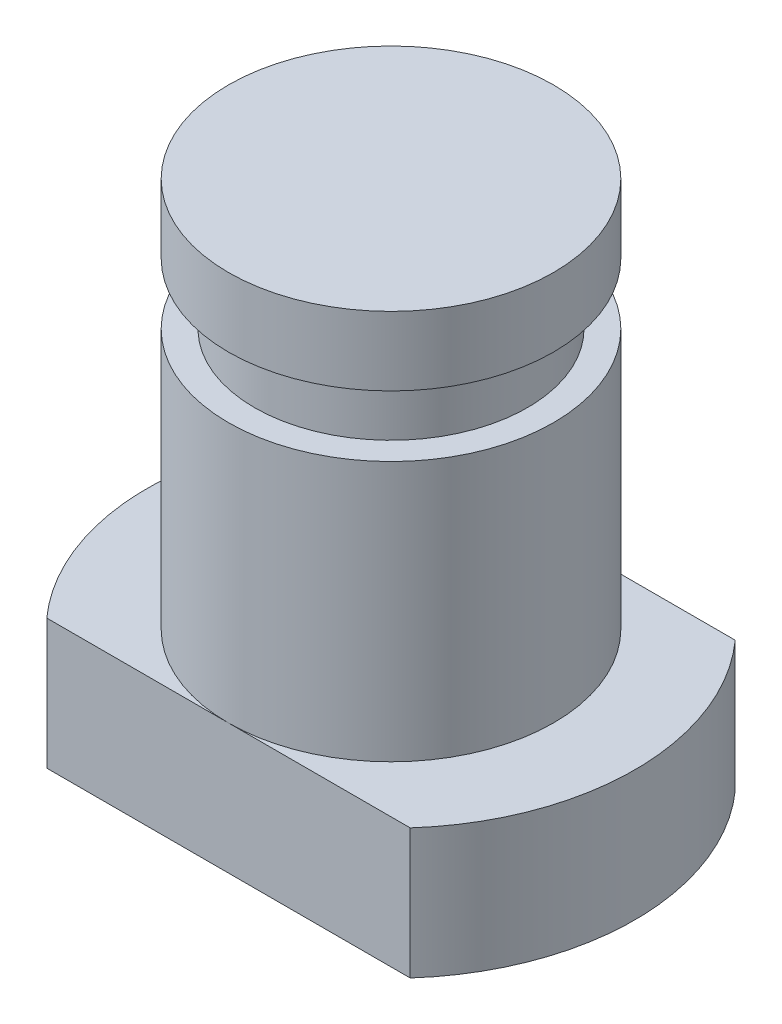
SolidWorks part; units mm, degrees
ref_plane "Front Plane" through (0, 0, 0) normal (0, 0, 1) x (1, 0, 0)
ref_plane "Top Plane" through (0, 0, 0) normal (0, 1, 0) x (1, 0, 0)
ref_plane "Right Plane" through (0, 0, 0) normal (1, 0, 0) x (0, 0, -1)
sketch "Sketch1" plane through (0, 0, 0) normal (0, 1, 0) x (1, 0, 0)
  circle A0 centre (0, 0) radius 3.175
  dimension "D1" = 6.35
extrude "Boss-Extrude1" add sketch "Sketch1" along normal blind 7.62
sketch "Sketch2" plane through (0, 0, 0) normal (0, -1, 0) x (1, 0, 0)
  line L0 (-10.6761, 0) -> (14.4716, 0) construction
  line L1 (-3.5498, 3.175) -> (3.5498, 3.175)
  line L2 (-3.5498, -3.175) -> (3.5498, -3.175)
  circle A2 centre (0, 0) radius 3.175 construction
  arc A3 (-3.5498, 3.175) -> (-3.5498, -3.175) centre (0, 0) ccw
  arc A4 (3.5498, -3.175) -> (3.5498, 3.175) centre (0, 0) ccw
  point P11 (-3.5498, 3.175)
  point P12 (3.5498, 3.175)
  point P13 (-3.5498, -3.175)
  point P14 (3.5498, -3.175)
  circle M4 centre (0, 0) radius 3.175
  dimension "D1" = 9.525
extrude "Boss-Extrude2" add sketch "Sketch2" along normal blind 2.54 contours L0 M4 | L0 A4 M4 | L0 A4 M4 | L0 M4 | L1 A4 L2 A3 region at (0, 0, 1.3475) region at (0, 0, -1.3475) region at (3.3375, 0, 1.7399) region at (3.3375, 0, -1.7399)
ref_plane "Plane1" through (0, 5.08, 0) normal (0, 1, 0) x (1, 0, 0)
sketch "Sketch6" plane through (0, 5.08, 0) normal (0, 1, 0) x (1, 0, 0)
  circle A0 centre (0, 0) radius 2.667
  dimension "D1" = 5.334
extrude "Cut-Extrude1" cut sketch "Sketch6" along normal blind 1.1938 flip side to cut
equation "\"0.3n\"=0.4"
